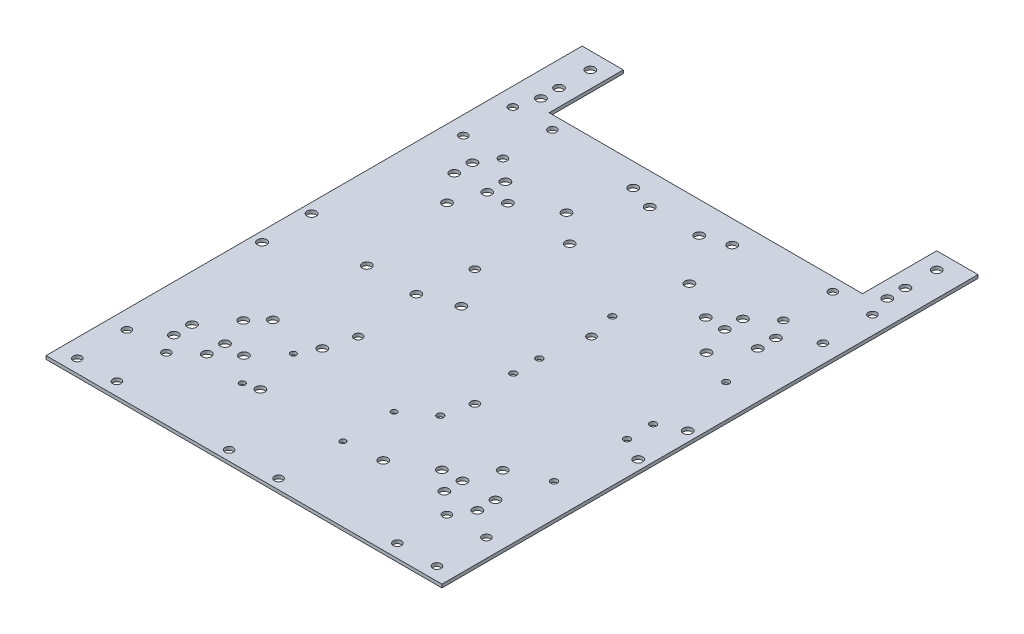
SolidWorks part; units mm, degrees
ref_plane "前视基准面" through (0, 0, 0) normal (0, 0, 1) x (1, 0, 0)
ref_plane "上视基准面" through (0, 0, 0) normal (0, 1, 0) x (1, 0, 0)
ref_plane "右视基准面" through (0, 0, 0) normal (1, 0, 0) x (0, 0, -1)
sketch "草图2" plane through (0, 0, 0) normal (0, 1, 0) x (1, 0, 0)
  line L0 (-120, 140) -> (-120, 185)
  line L1 (-95, 140) -> (95, 140)
  line L2 (-120, 140) -> (-120, -140)
  line L3 (-120, -140) -> (120, -140)
  line L4 (120, 140) -> (120, -140)
  line L5 (-120, 140) -> (120, -140) construction
  line L6 (-120, -140) -> (120, 140) construction
  line L7 (-120, 185) -> (-95, 185)
  line L8 (-95, 185) -> (-95, 140)
  line L9 (0, 140) -> (0, 250.6324) construction
  line L10 (95, 185) -> (95, 140)
  line L11 (120, 140) -> (120, 185)
  line L12 (120, 185) -> (95, 185)
  point P0 (0, 0)
  dimension "D1" = 280
  dimension "D2" = 240
  dimension "D3" = 190
  dimension "D4" = 45
base flange "基体-法兰2" sketch "草图2" thickness 2 reverse thickness direction no parameters "D1"=2.7366
sketch "草图26" plane through (0, 0, 0) normal (0, 1, 0) x (1, 0, 0)
  line L0 (-109, 117) -> (-85, 117) construction
  line L1 (-97, 110.9114) -> (-97, 117) construction
  line L2 (-120, 185) -> (-120, -140) construction
  line L3 (95, 140) -> (-95, 140) construction
  line L4 (0, 0) -> (-116.7374, 0) construction
  line L5 (0, 0) -> (0, 140) construction
  line L6 (-97, -110.9114) -> (-97, -117) construction
  line L7 (-109, -117) -> (-85, -117) construction
  line L8 (97, 110.9114) -> (97, 117) construction
  line L9 (109, 117) -> (85, 117) construction
  line L10 (109, -117) -> (85, -117) construction
  line L11 (97, -110.9114) -> (97, -117) construction
  circle A0 centre (-109, 102) radius 2.5
  circle A1 centre (-109, 132) radius 2.5
  circle A2 centre (-85, 132) radius 2.5
  circle A3 centre (-85, 102) radius 2.5
  circle A4 centre (-85, -102) radius 2.5
  circle A5 centre (-85, -132) radius 2.5
  circle A6 centre (-109, -132) radius 2.5
  circle A7 centre (-109, -102) radius 2.5
  circle A8 centre (85, 102) radius 2.5
  circle A9 centre (85, 132) radius 2.5
  circle A10 centre (109, 132) radius 2.5
  circle A11 centre (109, 102) radius 2.5
  circle A12 centre (109, -102) radius 2.5
  circle A13 centre (109, -132) radius 2.5
  circle A14 centre (85, -132) radius 2.5
  circle A15 centre (85, -102) radius 2.5
  dimension "D2" = 5
  dimension "D1" = 30
  dimension "D3" = 24
  dimension "D4" = 15
  dimension "D5" = 23
  dimension "D6" = 23
extrude "切除-拉伸1" cut sketch "草图26" against normal through all normal cut yes
sketch "草图27" plane through (0, -2, 0) normal (0, -1, 0) x (1, 0, 0)
  line L0 (0, 0) -> (0, 130.6645) construction
  line L2 (-35.3553, 35.3553) -> (0, 0) construction
  circle A0 centre (0, 0) radius 50 construction
  circle A1 centre (-35.3553, 35.3553) radius 2.5
  circle A2 centre (35.3553, 35.3553) radius 2.5
  circle A3 centre (35.3553, -35.3553) radius 2.5
  circle A4 centre (-35.3553, -35.3553) radius 2.5
  point P17 (0, 0)
  dimension "D1" = 100
  dimension "D2" = 5
  dimension "D3" = 45
  dimension "D4" = 4
extrude "切除-拉伸2" cut sketch "草图27" against normal blind 10 normal cut yes
sketch "草图28" plane through (0, -2, 0) normal (0, -1, 0) x (1, 0, 0)
  line L0 (0, 0) -> (119.9543, 0) construction
  line L2 (0, 0) -> (0, -100) construction
  circle A0 centre (0, 0) radius 100 construction
  circle A1 centre (-60, -80) radius 2.75
  circle A2 centre (-37.25, -92.8032) radius 2.75
  circle A3 centre (-78.6611, -61.7449) radius 2.75
  circle A4 centre (78.6611, -61.7449) radius 2.75
  circle A5 centre (37.25, -92.8032) radius 2.75
  circle A6 centre (60, -80) radius 2.75
  circle A7 centre (-78.6611, 61.7449) radius 2.75
  circle A8 centre (-37.25, 92.8032) radius 2.75
  circle A9 centre (-60, 80) radius 2.75
  circle A10 centre (60, 80) radius 2.75
  circle A11 centre (37.25, 92.8032) radius 2.75
  circle A12 centre (78.6611, 61.7449) radius 2.75
  point P13 (0, 0)
  point P16 (0, 0)
  dimension "D1" = 200
  dimension "D2" = 5.5
  dimension "D4" = 2
  dimension "D5" = 2
extrude "切除-拉伸3" cut sketch "草图28" against normal blind 10 normal cut yes
ref_plane "基准面1" through (95, 0, -140) normal (-1, 0, 0) x (0, 0, 1)
sketch "草图29" plane through (0, -2, 0) normal (0, -1, 0) x (1, 0, 0)
  line L0 (120, -185) -> (95, -185) construction
  line L1 (105, -145) -> (105, -175) construction
  line L2 (120, 140) -> (120, -185) construction
  circle A0 centre (105, -175) radius 2.75
  circle A1 centre (105, -156) radius 2.75
  circle A2 centre (105, -145) radius 2.75
  dimension "D4" = 5.5
  dimension "D1" = 10
  dimension "D2" = 19
  dimension "D3" = 11
  dimension "D5" = 15
extrude "切除-拉伸4" cut sketch "草图29" against normal blind 10 normal cut yes
mirror "镜向1" about plane through (0, 0, 0) normal (1, 0, 0) of "切除-拉伸4"
sketch "草图30" plane through (0, 0, 0) normal (0, 1, 0) x (1, 0, 0)
  line L0 (-35.7101, 85) -> (-96.3912, 85) construction
  line L1 (-120, 185) -> (-120, -140) construction
  circle A0 centre (-92, 90.5) radius 2.75
  circle A1 centre (-92, 79.5) radius 2.75
  circle A2 centre (-72, 79.5) radius 2.75
  circle A3 centre (-72, 90.5) radius 2.75
  dimension "D4" = 5.5
  dimension "D1" = 11
  dimension "D2" = 85
  dimension "D5" = 28
  dimension "D3" = 2
extrude "切除-拉伸5" cut sketch "草图30" against normal blind 10 normal cut yes
mirror "镜向2" about plane through (0, 0, 0) normal (0, 0, 1) of "切除-拉伸5"
mirror "镜向3" about plane through (0, 0, 0) normal (1, 0, 0) of "镜向2", "切除-拉伸5"
sketch "草图31" plane through (0, 0, 0) normal (0, 1, 0) x (1, 0, 0)
  line L0 (100, -29.87) -> (31.05, -29.87) construction
  line L1 (65.525, -29.87) -> (65.525, -52) construction
  line L4 (120, -140) -> (120, 185) construction
  circle A0 centre (31.05, -52) radius 2
  circle A1 centre (31.05, -7.74) radius 2
  circle A2 centre (100, -7.74) radius 2
  circle A3 centre (100, -52) radius 2
  circle A4 centre (-92, -79.5) radius 2.75 construction
  dimension "D4" = 27.5
  dimension "D5" = 4
  dimension "D1" = 44.26
  dimension "D2" = 68.95
  dimension "D3" = 20
extrude "切除-拉伸6" cut sketch "草图31" against normal blind 10 normal cut yes
pattern_linear "阵列(线性)1" count 2 spacing 60 along (0, 0, -1) of "切除-拉伸6"
sketch "草图32" plane through (0, 0, 0) normal (0, 1, 0) x (1, 0, 0)
  line L0 (-40, 44.65) -> (-20, 44.65) construction
  line L1 (-120, 185) -> (-120, -140) construction
  circle A0 centre (-20, 77.5) radius 2.75
  circle A1 centre (-20, 11.8) radius 2.75
  circle A2 centre (-72, 79.5) radius 2.75 construction
  dimension "D3" = 5.5
  dimension "D1" = 100
  dimension "D2" = 20
  dimension "D4" = 65.7
  dimension "D5" = 2
extrude "切除-拉伸7" cut sketch "草图32" against normal blind 10 normal cut yes
sketch "草图33" plane through (0, 0, 0) normal (0, 1, 0) x (1, 0, 0)
  line L0 (-40, -24) -> (-120, -24) construction
  line L1 (-120, 185) -> (-120, -140) construction
  line L2 (-120, 185) -> (-120, -140) construction
  circle A0 centre (-70, -52.5) radius 2.75
  circle A1 centre (-70, 4.5) radius 2.75
  circle A2 centre (-40, 4.5) radius 2.75
  circle A3 centre (-40, -52.5) radius 2.75
  circle A4 centre (-92, -79.5) radius 2.75 construction
  dimension "D1" = 57
  dimension "D2" = 5.5
  dimension "D4" = 27
  dimension "D5" = 50
  dimension "D3" = 2
extrude "切除-拉伸8" cut sketch "草图33" against normal blind 10 normal cut yes
sketch "草图34" plane through (0, 0, 0) normal (0, 1, 0) x (1, 0, 0)
  line L0 (-15.5, -79.5) -> (-15.5, -95) construction
  line L1 (15, -79.5) -> (-15.5, -79.5) construction
  line L4 (-120, 185) -> (-120, -140) construction
  line L5 (-120, -140) -> (120, -140) construction
  circle A0 centre (15, -95) radius 1.75
  circle A1 centre (15, -64) radius 1.75
  circle A2 centre (-46, -64) radius 1.75
  circle A3 centre (-46, -95) radius 1.75
  point P12 (0, -87.8243)
  point P13 (0, 0)
  point P14 (0, 0)
  point P15 (0, -90.6523)
  point P16 (0, -92.682)
  point P17 (0, -58.4362)
  point P18 (0, 0)
  point P19 (0, 0)
  point P20 (-54.7053, -63.0254)
  point P21 (0, -74.8423)
  point P22 (-27.5404, -92.4843)
  point P23 (-16.5129, -76.2465)
  dimension "D3" = 3.5
  dimension "D1" = 61
  dimension "D2" = 31
  dimension "D4" = 74
  dimension "D5" = 45
extrude "切除-拉伸9" cut sketch "草图34" against normal blind 10 normal cut yes
sketch "草图35" plane through (0, -2, 0) normal (0, -1, 0) x (1, 0, 0)
  line L0 (0, 0) -> (0, -140) construction
  line L1 (95, -140) -> (-95, -140) construction
  circle A0 centre (30, -126) radius 2.75
  circle A1 centre (-30, -126) radius 2.75
  dimension "D3" = 5.5
  dimension "D1" = 60
  dimension "D2" = 14
extrude "切除-拉伸10" cut sketch "草图35" against normal blind 10 normal cut yes
sketch "草图36" plane through (0, -2, 0) normal (0, -1, 0) x (1, 0, 0)
  line L0 (0, 0) -> (-120, 0) construction
  line L1 (-120, -185) -> (-120, 140) construction
  line L2 (0, 0) -> (0, 140) construction
  line L3 (-120, 140) -> (120, 140) construction
  line L4 (0, -121) -> (0, 0) construction
  circle A0 centre (-114, -15) radius 2.75
  circle A1 centre (-114, 15) radius 2.75
  circle A2 centre (114, -15) radius 2.75
  circle A3 centre (114, 15) radius 2.75
  circle A4 centre (15, 134) radius 2.5
  circle A5 centre (-15, 134) radius 2.5
  circle A6 centre (15, -121) radius 2.75
  circle A7 centre (-15, -121) radius 2.75
  circle A8 centre (30, -126) radius 2.75 construction
  point P23 (0, -140.216)
  point P24 (0, -139.7632)
  point P25 (0, -139.7873)
  point P26 (0, -69.6699)
  point P27 (0, -4.189)
  point P28 (0, -139.9953)
  point P29 (0, -126.9955)
  point P30 (0, 0)
  point P33 (15, -115.2051)
  dimension "D1" = 30
  dimension "D2" = 5.5
  dimension "D4" = 5
  dimension "D7" = 5.5
  dimension "D9" = 5
  dimension "D3" = 6
  dimension "D5" = 30
  dimension "D6" = 6
  dimension "D8" = 15
extrude "切除-拉伸11" cut sketch "草图36" against normal blind 10 normal cut yes
sketch "折弯-线3" plane through (0, 0, 0) normal (0, 1, 0) x (1, 0, 0)
sketch "边界框3" plane through (0, 0, 0) normal (0, 1, 0) x (1, 0, 0)
sheet metal parameters "钣金7" thickness 2 parameters "D1"=2.7366
flat pattern "平板型式7" [suppressed]
sketch "折弯-线4" plane through (0, 0, 0) normal (0, 1, 0) x (1, 0, 0)
sketch "边界框4" [suppressed] plane through (0, 0, 0) normal (0, 1, 0) x (1, 0, 0)
sheet metal parameters "钣金12" thickness 2 parameters "D1"=2.7366
flat pattern "平板型式7"
sketch "折弯-线4" plane through (0, 0, 0) normal (0, 1, 0) x (1, 0, 0)
sketch "边界框4" [suppressed] plane through (0, 0, 0) normal (0, 1, 0) x (1, 0, 0)
sheet metal parameters "钣金13" thickness 2 parameters "D1"=2.7366
flat pattern "平板型式7"
sketch "折弯-线4" plane through (0, 0, 0) normal (0, 1, 0) x (1, 0, 0)
sketch "边界框4" [suppressed] plane through (0, 0, 0) normal (0, 1, 0) x (1, 0, 0)
sheet metal parameters "钣金14" thickness 2 parameters "D1"=2.7366
flat pattern "平板型式7"
sketch "折弯-线4" plane through (0, 0, 0) normal (0, 1, 0) x (1, 0, 0)
sketch "边界框4" [suppressed] plane through (0, 0, 0) normal (0, 1, 0) x (1, 0, 0)
sheet metal parameters "钣金26" thickness 2 parameters "D1"=2.7366
flat pattern "平板型式7"
sketch "折弯-线4" plane through (0, 0, 0) normal (0, 1, 0) x (1, 0, 0)
sketch "边界框4" [suppressed] plane through (0, 0, 0) normal (0, 1, 0) x (1, 0, 0)
sheet metal parameters "钣金27" thickness 2 parameters "D1"=2.7366
flat pattern "平板型式7"
sketch "折弯-线4" plane through (0, 0, 0) normal (0, 1, 0) x (1, 0, 0)
sketch "边界框4" [suppressed] plane through (0, 0, 0) normal (0, 1, 0) x (1, 0, 0)
sheet metal parameters "钣金28" thickness 2 parameters "D1"=2.7366
flat pattern "平板型式7"
sketch "折弯-线4" plane through (0, 0, 0) normal (0, 1, 0) x (1, 0, 0)
sketch "边界框4" [suppressed] plane through (0, 0, 0) normal (0, 1, 0) x (1, 0, 0)
sheet metal parameters "钣金29" thickness 2 parameters "D1"=2.7366
flat pattern "平板型式7"
sketch "折弯-线4" plane through (0, 0, 0) normal (0, 1, 0) x (1, 0, 0)
sketch "边界框4" [suppressed] plane through (0, 0, 0) normal (0, 1, 0) x (1, 0, 0)
sheet metal parameters "钣金30" thickness 2 parameters "D1"=2.7366
flat pattern "平板型式7"
sketch "折弯-线4" plane through (0, 0, 0) normal (0, 1, 0) x (1, 0, 0)
sketch "边界框4" [suppressed] plane through (0, 0, 0) normal (0, 1, 0) x (1, 0, 0)
sheet metal parameters "钣金31" thickness 2 parameters "D1"=2.7366
flat pattern "平板型式7"
sketch "折弯-线4" plane through (0, 0, 0) normal (0, 1, 0) x (1, 0, 0)
sketch "边界框4" [suppressed] plane through (0, 0, 0) normal (0, 1, 0) x (1, 0, 0)
sheet metal parameters "钣金32" thickness 2 parameters "D1"=2.7366
flat pattern "平板型式7"
sketch "折弯-线4" plane through (0, 0, 0) normal (0, 1, 0) x (1, 0, 0)
sketch "边界框4" [suppressed] plane through (0, 0, 0) normal (0, 1, 0) x (1, 0, 0)
sheet metal parameters "钣金33" thickness 2 parameters "D1"=2.7366
flat pattern "平板型式7"
sketch "折弯-线4" plane through (0, 0, 0) normal (0, 1, 0) x (1, 0, 0)
sketch "边界框4" [suppressed] plane through (0, 0, 0) normal (0, 1, 0) x (1, 0, 0)
sheet metal parameters "钣金34" thickness 2 parameters "D1"=2.7366
flat pattern "平板型式7"
sketch "折弯-线4" plane through (0, 0, 0) normal (0, 1, 0) x (1, 0, 0)
sketch "边界框4" [suppressed] plane through (0, 0, 0) normal (0, 1, 0) x (1, 0, 0)
sheet metal parameters "钣金35" thickness 2 parameters "D1"=2.7366
flat pattern "平板型式7"
sketch "折弯-线4" plane through (0, 0, 0) normal (0, 1, 0) x (1, 0, 0)
sketch "边界框4" [suppressed] plane through (0, 0, 0) normal (0, 1, 0) x (1, 0, 0)
sheet metal parameters "钣金36" thickness 2 parameters "D1"=2.7366
flat pattern "平板型式7"
sketch "折弯-线4" plane through (0, 0, 0) normal (0, 1, 0) x (1, 0, 0)
sketch "边界框4" [suppressed] plane through (0, 0, 0) normal (0, 1, 0) x (1, 0, 0)
sheet metal parameters "钣金37" thickness 2 parameters "D1"=2.7366
flat pattern "平板型式7"
sketch "折弯-线4" plane through (0, 0, 0) normal (0, 1, 0) x (1, 0, 0)
sketch "边界框4" [suppressed] plane through (0, 0, 0) normal (0, 1, 0) x (1, 0, 0)
